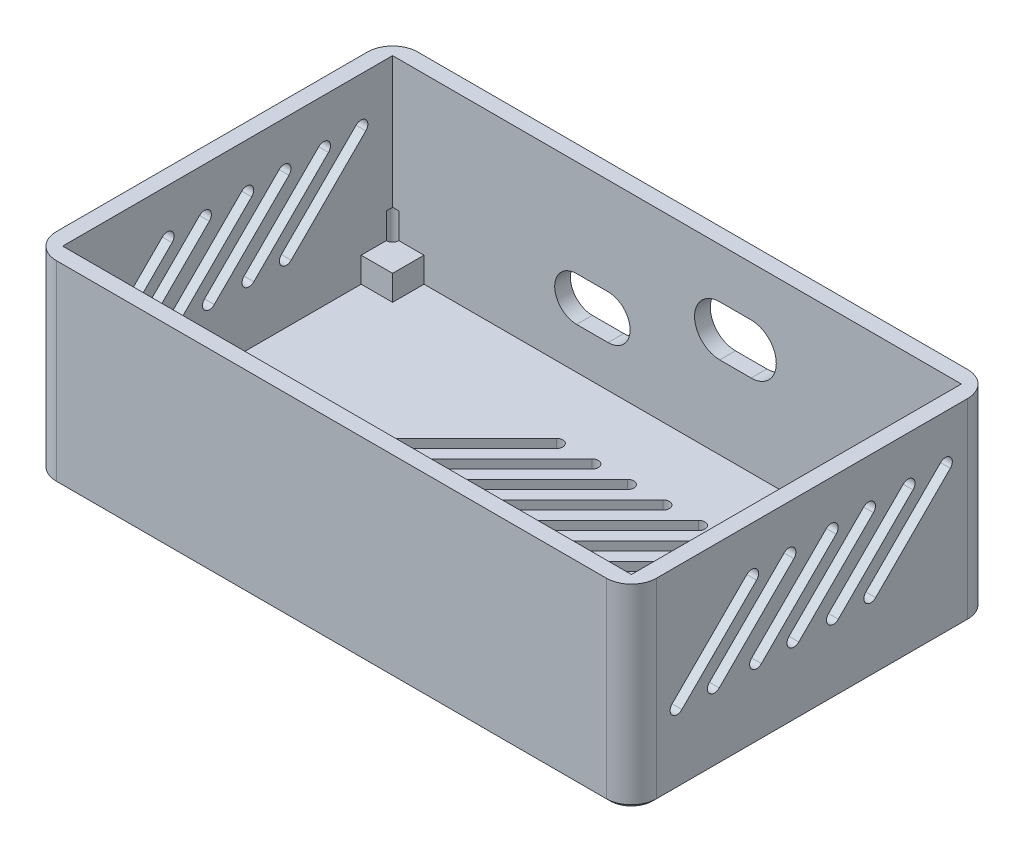
SolidWorks part; units mm, degrees
ref_plane "Front Plane" through (0, 0, 0) normal (0, 0, 1) x (1, 0, 0)
ref_plane "Top Plane" through (0, 0, 0) normal (0, 1, 0) x (1, 0, 0)
ref_plane "Right Plane" through (0, 0, 0) normal (1, 0, 0) x (0, 0, -1)
sketch "Croquis_contorno" plane through (0, 0, 0) normal (0, 1, 0) x (1, 0, 0)
  line L0 (-43.75, -28.75) -> (43.75, -28.75)
  line L1 (47.75, -24.75) -> (47.75, 24.75)
  line L2 (43.75, 28.75) -> (-43.75, 28.75)
  line L3 (-47.75, 24.75) -> (-47.75, -24.75)
  arc A0 (43.75, -28.75) -> (47.75, -24.75) centre (43.75, -24.75) ccw
  arc A1 (47.75, 24.75) -> (43.75, 28.75) centre (43.75, 24.75) ccw
  arc A2 (-43.75, 28.75) -> (-47.75, 24.75) centre (-43.75, 24.75) ccw
  arc A3 (-47.75, -24.75) -> (-43.75, -28.75) centre (-43.75, -24.75) ccw
  dimension "D3" = 4
  dimension "D1" = 95.5
  dimension "D2" = 57.5
extrude "Cuerpo" add sketch "Croquis_contorno" along normal blind 31
ref_plane "Plano_Top Plane_+31" through (0, 31, 0) normal (0, 1, 0) x (1, 0, 0)
sketch "Croquis_hueco_PCB" plane through (0, 31, 0) normal (0, 1, 0) x (1, 0, 0)
  line L1 (-45.25, -26.25) -> (45.25, -26.25)
  line L2 (-45.25, -26.25) -> (-45.25, 26.25)
  line L3 (-45.25, 26.25) -> (45.25, 26.25)
  line L4 (45.25, -26.25) -> (45.25, 26.25)
  line L5 (-45.25, -26.25) -> (45.25, 26.25) construction
  line L6 (-45.25, 26.25) -> (45.25, -26.25) construction
  dimension "D1" = 90.5
  dimension "D2" = 52.5
extrude "Hueco_PCB" cut sketch "Croquis_hueco_PCB" against normal blind 29
ref_plane "Plano_Top Plane_+2" through (0, 2, 0) normal (0, 1, 0) x (1, 0, 0)
sketch "Croquis_apoyos" plane through (0, 2, 0) normal (0, 1, 0) x (1, 0, 0)
  line L0 (45.25, 26.25) -> (-45.25, 26.25) construction
  line L1 (-45.25, -26.25) -> (-40.25, -26.25)
  line L2 (-45.25, -26.25) -> (-45.25, -21.25)
  line L3 (-45.25, -21.25) -> (-40.25, -21.25)
  line L4 (-40.25, -26.25) -> (-40.25, -21.25)
  line L5 (-45.25, -26.25) -> (-40.25, -21.25) construction
  line L6 (-45.25, -21.25) -> (-40.25, -26.25) construction
  line L7 (-45.25, 21.25) -> (-40.25, 21.25)
  line L8 (-45.25, 21.25) -> (-45.25, 26.25)
  line L9 (-45.25, 26.25) -> (-40.25, 26.25)
  line L10 (-40.25, 21.25) -> (-40.25, 26.25)
  line L11 (-45.25, 21.25) -> (-40.25, 26.25) construction
  line L12 (-45.25, 26.25) -> (-40.25, 21.25) construction
  line L13 (45.25, -26.25) -> (45.25, 26.25) construction
  line L14 (40.25, -26.25) -> (45.25, -26.25)
  line L15 (40.25, -26.25) -> (40.25, -21.25)
  line L16 (40.25, -21.25) -> (45.25, -21.25)
  line L17 (45.25, -26.25) -> (45.25, -21.25)
  line L18 (40.25, -26.25) -> (45.25, -21.25) construction
  line L19 (40.25, -21.25) -> (45.25, -26.25) construction
  line L21 (40.25, 21.25) -> (45.25, 21.25)
  line L22 (40.25, 21.25) -> (40.25, 26.25)
  line L23 (40.25, 26.25) -> (45.25, 26.25)
  line L24 (45.25, 21.25) -> (45.25, 26.25)
  line L25 (40.25, 21.25) -> (45.25, 26.25) construction
  line L26 (40.25, 26.25) -> (45.25, 21.25) construction
  point P0 (-42.75, 23.75)
  point P11 (42.75, -23.75)
  point P18 (42.75, 23.75)
  dimension "D1" = 5
  dimension "D2" = 5
extrude "Apoyos_PCB" add sketch "Croquis_apoyos" along normal blind 4
sketch "Croquis_alivios" plane through (0, 2, 0) normal (0, 1, 0) x (1, 0, 0)
  circle A0 centre (-45.25, -26.25) radius 1
  circle A1 centre (-45.25, 26.25) radius 1
  circle A2 centre (45.25, -26.25) radius 1
  circle A3 centre (45.25, 26.25) radius 1
  dimension "D1" = 2
extrude "Alivios_esquinas" cut sketch "Croquis_alivios" along normal blind 8.1
sketch "Croquis_salidas" plane through (0, 0, 0) normal (0, 0, 1) x (1, 0, 0)
  line L0 (6.8, 19.1) -> (11.8, 19.1) construction
  line L1 (6.8, 23.1) -> (11.8, 23.1)
  line L2 (6.8, 15.1) -> (11.8, 15.1)
  line L3 (-15.96, 12.1) -> (-10.96, 12.1) construction
  line L4 (-15.96, 15.6) -> (-10.96, 15.6)
  line L5 (-15.96, 8.6) -> (-10.96, 8.6)
  arc A0 (6.8, 23.1) -> (6.8, 15.1) centre (6.8, 19.1) ccw
  arc A1 (11.8, 15.1) -> (11.8, 23.1) centre (11.8, 19.1) ccw
  arc A2 (-15.96, 15.6) -> (-15.96, 8.6) centre (-15.96, 12.1) ccw
  arc A3 (-10.96, 8.6) -> (-10.96, 15.6) centre (-10.96, 12.1) ccw
  point P2 (9.3, 19.1)
  point P7 (-13.46, 12.1)
  point P14 (0, 0)
extrude "Salidas_USB_y_panel" cut sketch "Croquis_salidas" against normal through all
sketch "Croquis_ventilas" plane through (0, 0, 0) normal (1, 0, 0) x (0, 0, -1)
  line L0 (-21.496, 11.6603) -> (-9.6167, 23.5397) construction
  line L1 (-22.2739, 12.4381) -> (-10.3945, 24.3175)
  line L2 (-20.7182, 10.8825) -> (-8.8388, 22.7619)
  line L3 (-15.5563, 11.6603) -> (-3.677, 23.5397) construction
  line L4 (-16.3342, 12.4381) -> (-4.4548, 24.3175)
  line L5 (-14.7785, 10.8825) -> (-2.8991, 22.7619)
  line L6 (-8.8388, 11.6603) -> (3.0406, 23.5397) construction
  line L7 (-9.6167, 12.4381) -> (2.2627, 24.3175)
  line L8 (-8.061, 10.8825) -> (3.8184, 22.7619)
  line L9 (-2.8991, 11.6603) -> (8.9803, 23.5397) construction
  line L10 (-3.677, 12.4381) -> (8.2024, 24.3175)
  line L11 (-2.1213, 10.8825) -> (9.7581, 22.7619)
  line L12 (3.3941, 11.6603) -> (15.2735, 23.5397) construction
  line L13 (2.6163, 12.4381) -> (14.4957, 24.3175)
  line L14 (4.1719, 10.8825) -> (16.0513, 22.7619)
  line L15 (9.3338, 11.6603) -> (21.2132, 23.5397) construction
  line L16 (8.556, 12.4381) -> (20.4354, 24.3175)
  line L17 (10.1116, 10.8825) -> (21.991, 22.7619)
  arc A0 (-22.2739, 12.4381) -> (-20.7182, 10.8825) centre (-21.496, 11.6603) ccw
  arc A1 (-8.8388, 22.7619) -> (-10.3945, 24.3175) centre (-9.6167, 23.5397) ccw
  arc A2 (-16.3342, 12.4381) -> (-14.7785, 10.8825) centre (-15.5563, 11.6603) ccw
  arc A3 (-2.8991, 22.7619) -> (-4.4548, 24.3175) centre (-3.677, 23.5397) ccw
  arc A4 (-9.6167, 12.4381) -> (-8.061, 10.8825) centre (-8.8388, 11.6603) ccw
  arc A5 (3.8184, 22.7619) -> (2.2627, 24.3175) centre (3.0406, 23.5397) ccw
  arc A6 (-3.677, 12.4381) -> (-2.1213, 10.8825) centre (-2.8991, 11.6603) ccw
  arc A7 (9.7581, 22.7619) -> (8.2024, 24.3175) centre (8.9803, 23.5397) ccw
  arc A8 (2.6163, 12.4381) -> (4.1719, 10.8825) centre (3.3941, 11.6603) ccw
  arc A9 (16.0513, 22.7619) -> (14.4957, 24.3175) centre (15.2735, 23.5397) ccw
  arc A10 (8.556, 12.4381) -> (10.1116, 10.8825) centre (9.3338, 11.6603) ccw
  arc A11 (21.991, 22.7619) -> (20.4354, 24.3175) centre (21.2132, 23.5397) ccw
  point P2 (-15.5563, 17.6)
  point P7 (-9.6167, 17.6)
  point P14 (-2.8991, 17.6)
  point P21 (3.0406, 17.6)
  point P28 (9.3338, 17.6)
  point P35 (15.2735, 17.6)
  point P42 (0, 0)
extrude "Ventilas_laterales" cut sketch "Croquis_ventilas" along normal through all and the other way through all
sketch "Croquis_rejilla_piso" plane through (0, 0, 0) normal (0, 1, 0) x (1, 0, 0)
  line L0 (-37.4767, -14.8492) -> (-7.7782, 14.8492) construction
  line L1 (-38.1838, -14.1421) -> (-8.4853, 15.5563)
  line L2 (-36.7696, -15.5563) -> (-7.0711, 14.1421)
  line L3 (-31.8198, -14.8492) -> (-2.1213, 14.8492) construction
  line L4 (-32.5269, -14.1421) -> (-2.8284, 15.5563)
  line L5 (-31.1127, -15.5563) -> (-1.4142, 14.1421)
  line L6 (-26.163, -14.8492) -> (3.5355, 14.8492) construction
  line L7 (-26.8701, -14.1421) -> (2.8284, 15.5563)
  line L8 (-25.4558, -15.5563) -> (4.2426, 14.1421)
  line L9 (-20.5061, -14.8492) -> (9.1924, 14.8492) construction
  line L10 (-21.2132, -14.1421) -> (8.4853, 15.5563)
  line L11 (-19.799, -15.5563) -> (9.8995, 14.1421)
  line L12 (-14.8492, -14.8492) -> (14.8492, 14.8492) construction
  line L13 (-15.5563, -14.1421) -> (14.1421, 15.5563)
  line L14 (-14.1421, -15.5563) -> (15.5563, 14.1421)
  line L15 (-9.1924, -14.8492) -> (20.5061, 14.8492) construction
  line L16 (-9.8995, -14.1421) -> (19.799, 15.5563)
  line L17 (-8.4853, -15.5563) -> (21.2132, 14.1421)
  line L18 (-3.5355, -14.8492) -> (26.163, 14.8492) construction
  line L19 (-4.2426, -14.1421) -> (25.4558, 15.5563)
  line L20 (-2.8284, -15.5563) -> (26.8701, 14.1421)
  line L21 (2.1213, -14.8492) -> (31.8198, 14.8492) construction
  line L22 (1.4142, -14.1421) -> (31.1127, 15.5563)
  line L23 (2.8284, -15.5563) -> (32.5269, 14.1421)
  line L24 (7.7782, -14.8492) -> (37.4767, 14.8492) construction
  line L25 (7.0711, -14.1421) -> (36.7696, 15.5563)
  line L26 (8.4853, -15.5563) -> (38.1838, 14.1421)
  arc A0 (-38.1838, -14.1421) -> (-36.7696, -15.5563) centre (-37.4767, -14.8492) ccw
  arc A1 (-7.0711, 14.1421) -> (-8.4853, 15.5563) centre (-7.7782, 14.8492) ccw
  arc A2 (-32.5269, -14.1421) -> (-31.1127, -15.5563) centre (-31.8198, -14.8492) ccw
  arc A3 (-1.4142, 14.1421) -> (-2.8284, 15.5563) centre (-2.1213, 14.8492) ccw
  arc A4 (-26.8701, -14.1421) -> (-25.4558, -15.5563) centre (-26.163, -14.8492) ccw
  arc A5 (4.2426, 14.1421) -> (2.8284, 15.5563) centre (3.5355, 14.8492) ccw
  arc A6 (-21.2132, -14.1421) -> (-19.799, -15.5563) centre (-20.5061, -14.8492) ccw
  arc A7 (9.8995, 14.1421) -> (8.4853, 15.5563) centre (9.1924, 14.8492) ccw
  arc A8 (-15.5563, -14.1421) -> (-14.1421, -15.5563) centre (-14.8492, -14.8492) ccw
  arc A9 (15.5563, 14.1421) -> (14.1421, 15.5563) centre (14.8492, 14.8492) ccw
  arc A10 (-9.8995, -14.1421) -> (-8.4853, -15.5563) centre (-9.1924, -14.8492) ccw
  arc A11 (21.2132, 14.1421) -> (19.799, 15.5563) centre (20.5061, 14.8492) ccw
  arc A12 (-4.2426, -14.1421) -> (-2.8284, -15.5563) centre (-3.5355, -14.8492) ccw
  arc A13 (26.8701, 14.1421) -> (25.4558, 15.5563) centre (26.163, 14.8492) ccw
  arc A14 (1.4142, -14.1421) -> (2.8284, -15.5563) centre (2.1213, -14.8492) ccw
  arc A15 (32.5269, 14.1421) -> (31.1127, 15.5563) centre (31.8198, 14.8492) ccw
  arc A16 (7.0711, -14.1421) -> (8.4853, -15.5563) centre (7.7782, -14.8492) ccw
  arc A17 (38.1838, 14.1421) -> (36.7696, 15.5563) centre (37.4767, 14.8492) ccw
  point P2 (-22.6274, 0)
  point P7 (-16.9706, 0)
  point P14 (-11.3137, 0)
  point P21 (-5.6569, 0)
  point P28 (0, 0)
  point P35 (5.6569, 0)
  point P42 (11.3137, 0)
  point P49 (16.9706, 0)
  point P56 (22.6274, 0)
  point P63 (0, 0)
extrude "Rejilla_piso" cut sketch "Croquis_rejilla_piso" along normal blind 2
chamfer "Chaflan_base" distance 0.6 angle 45 8 edges at (0, 0, 28.75) (46.5784, 0, 27.5784) (47.75, 0, 0) (46.5784, 0, -27.5784) (0, 0, -28.75) (-46.5784, 0, -27.5784) (-47.75, 0, 0) (-46.5784, 0, 27.5784) tangent propagation no
